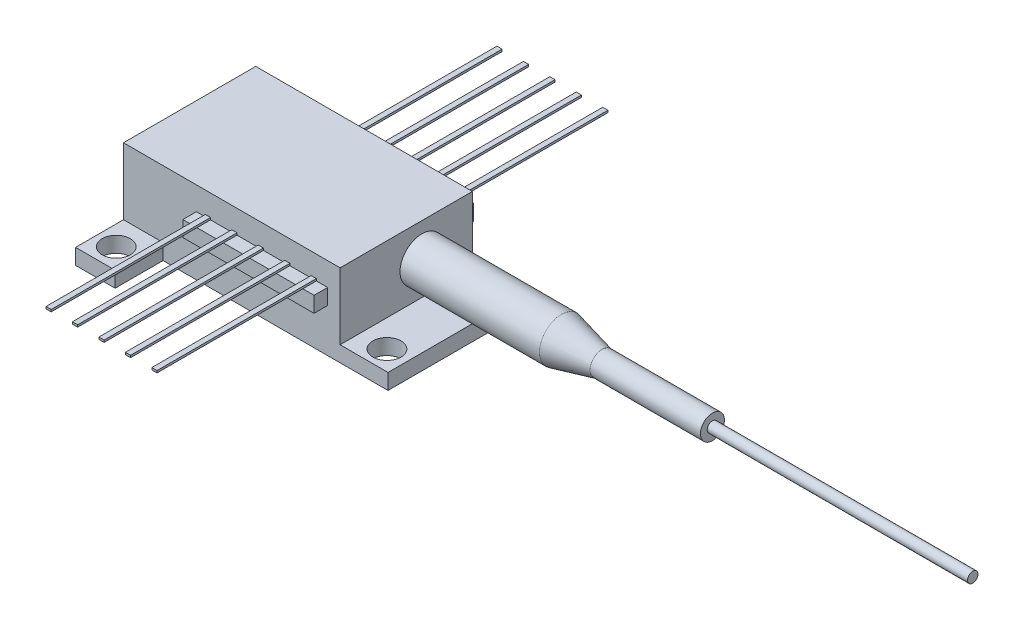
SolidWorks part; units mm, degrees
ref_plane "Front Plane" through (0, 0, 0) normal (0, 0, 1) x (1, 0, 0)
ref_plane "Top Plane" through (0, 0, 0) normal (0, 1, 0) x (1, 0, 0)
ref_plane "Right Plane" through (0, 0, 0) normal (1, 0, 0) x (0, 0, -1)
sketch "Sketch1" plane through (0, 0, 0) normal (0, 1, 0) x (1, 0, 0)
  line L1 (-10.4, -6.35) -> (10.4, -6.35)
  line L2 (-10.4, -6.35) -> (-10.4, 6.35)
  line L3 (-10.4, 6.35) -> (10.4, 6.35)
  line L4 (10.4, -6.35) -> (10.4, 6.35)
  line L5 (-10.4, -6.35) -> (10.4, 6.35) construction
  line L6 (-10.4, 6.35) -> (10.4, -6.35) construction
  point P0 (0, 0)
  dimension "D1" = 12.7
  dimension "D2" = 20.8
extrude "Boss-Extrude1" add sketch "Sketch1" along normal blind 6.4
sketch "Sketch3" plane through (0, 0, 0) normal (0, -1, 0) x (1, 0, 0)
  line L0 (-10.4, 6.35) -> (10.4, 6.35) construction
  line L1 (-10.4, 10.95) -> (-6.6, 10.95)
  line L2 (-10.4, 10.95) -> (-10.4, -10.95)
  line L3 (-10.4, 0) -> (15, 0) construction
  line L4 (15, 6.35) -> (15, -6.35)
  line L5 (-6.6, -6.35) -> (15, -6.35)
  line L6 (-6.6, 10.95) -> (-6.6, 6.35)
  line L7 (-6.6, 6.35) -> (15, 6.35)
  line L8 (-6.6, -10.95) -> (-6.6, -6.35)
  line L9 (-10.4, -10.95) -> (-6.6, -10.95)
  dimension "D1" = 25.4
  dimension "D2" = 10.95
  dimension "D3" = 3.8
extrude "Boss-Extrude2" add sketch "Sketch3" along normal blind 1.5
sketch "Sketch5" plane through (0, -1.5, 0) normal (0, -1, 0) x (1, 0, 0)
  line L0 (15, -6.35) -> (15, 6.35) construction
  line L1 (-10.4, 10.95) -> (-10.4, 6.35) construction
  circle A0 centre (-8.5, 8.95) radius 1.35
  circle A1 centre (13, 4.45) radius 1.35
  dimension "D1" = 2.7
  dimension "D2" = 4.45
  dimension "D3" = 2
  dimension "D4" = 8.95
  dimension "D5" = 1.9
extrude "Cut-Extrude1" cut sketch "Sketch5" against normal through all
mirror "Mirror3" about plane through (0, 0, 0) normal (0, 0, 1) of "Cut-Extrude1"
sketch "Sketch6" plane through (-10.4, 0, 0) normal (-1, 0, 0) x (0, 0, 1)
  line L0 (6.35, 6.4) -> (6.35, 0) construction
  line L1 (10.95, -1.5) -> (-10.95, -1.5) construction
  point P0 (1.85, 3.3)
  dimension "D1" = 4.5
  dimension "D2" = 4.8
ref_point "laser_out"
ref_axis "laser" through (-10.4, 3.3, 1.85) along (-1, 0, 0)
sketch "Sketch7" plane through (10.4, 0, 0) normal (1, 0, 0) x (0, 0, -1)
  line L0 (6.35, 6.4) -> (6.35, 0) construction
  line L1 (6.35, -1.5) -> (-6.35, -1.5) construction
  point P0 (1.5, 3.2)
  dimension "D1" = 4.85
  dimension "D2" = 4.7
ref_point "fiber_out"
ref_plane "Plane2" through (0, 3.2, 0) normal (0, -1, 0) x (-1, 0, 0)
ref_axis "fiber" through (10.4, 3.2, -1.5) along (1, 0, 0)
sketch "Sketch11" plane through (0, 3.2, 0) normal (0, -1, 0) x (-1, 0, 0)
  line L0 (-10.4, 1.5) -> (-10.4, 3.6)
  line L1 (-10.4, -6.35) -> (-10.4, 6.35) construction
  line L2 (-10.4, 3.6) -> (-23.8, 3.6)
  line L3 (-23.8, 3.6) -> (-27.7, 2.65)
  line L4 (-27.7, 2.65) -> (-38.3, 2.65)
  line L5 (-38.3, 2.65) -> (-38.3, 1.5)
  line L6 (-10.4, 1.5) -> (-61.1766, 1.5) construction
  line L7 (-38.3, 1.5) -> (-10.4, 1.5)
  line L9 (-15, 6.35) -> (-15, -6.35) construction
  dimension "D1" = 1.15
  dimension "D2" = 2.1
  dimension "D3" = 8.8
  dimension "D4" = 12.7
  dimension "D5" = 23.3
revolve "Revolve1" add sketch "Sketch11" angle 360 about axis through (10.4, 3.2, -1.5) along (1, 0, 0)
ref_plane "Plane1" through (0, 2.665, 0) normal (0, -1, 0) x (-1, 0, 0)
sketch "Sketch9" plane through (0, 2.665, 0) normal (0, -1, 0) x (-1, 0, 0)
  line L0 (10.4, -6.35) -> (-10.4, -6.35) construction
  line L1 (3.4, -6.35) -> (-9.2, -6.35)
  line L2 (3.4, -6.35) -> (3.4, -7.65)
  line L3 (3.4, -7.65) -> (-9.2, -7.65)
  line L4 (-9.2, -6.35) -> (-9.2, -7.65)
  line L6 (10.4, 6.35) -> (10.4, -6.35) construction
  line L7 (-10.4, -6.35) -> (-10.4, 6.35) construction
  dimension "D1" = 7.65
  dimension "D2" = 1.2
  dimension "D3" = 7
extrude "Boss-Extrude4" add sketch "Sketch9" against normal blind 1.5
sketch "Sketch10" plane through (0, 4.165, 0) normal (0, 1, 0) x (1, 0, 0)
  line L0 (-3.4, -6.35) -> (9.2, -6.35) construction
  line L1 (7.62, -6.35) -> (8.12, -6.35)
  line L2 (7.62, -6.35) -> (7.62, -21.65)
  line L3 (7.62, -21.65) -> (8.12, -21.65)
  line L4 (8.12, -6.35) -> (8.12, -21.65)
  line L5 (7.87, -6.35) -> (7.87, -21.65) construction
  line L6 (10.4, -6.35) -> (10.4, 6.35) construction
  dimension "D1" = 0.5
  dimension "D2" = 21.65
  dimension "D3" = 2.53
extrude "Boss-Extrude5" add sketch "Sketch10" along normal blind 0.2
pattern_linear "LPattern1" count 5 spacing 2.54 along (-1, 0, 0) of "Boss-Extrude5"
mirror "Mirror2" about plane through (0, 0, 0) normal (0, 0, 1) of "Boss-Extrude4", "Boss-Extrude5", "LPattern1"
sketch "Sketch12" plane through (38.3, 0, 0) normal (1, 0, 0) x (0, 0, -1)
  circle A0 centre (1.5, 3.2) radius 0.5
  circle A1 centre (1.5, 3.2) radius 1.15 construction
  dimension "D1" = 1
extrude "Boss-Extrude6" add sketch "Sketch12" along normal blind 25
